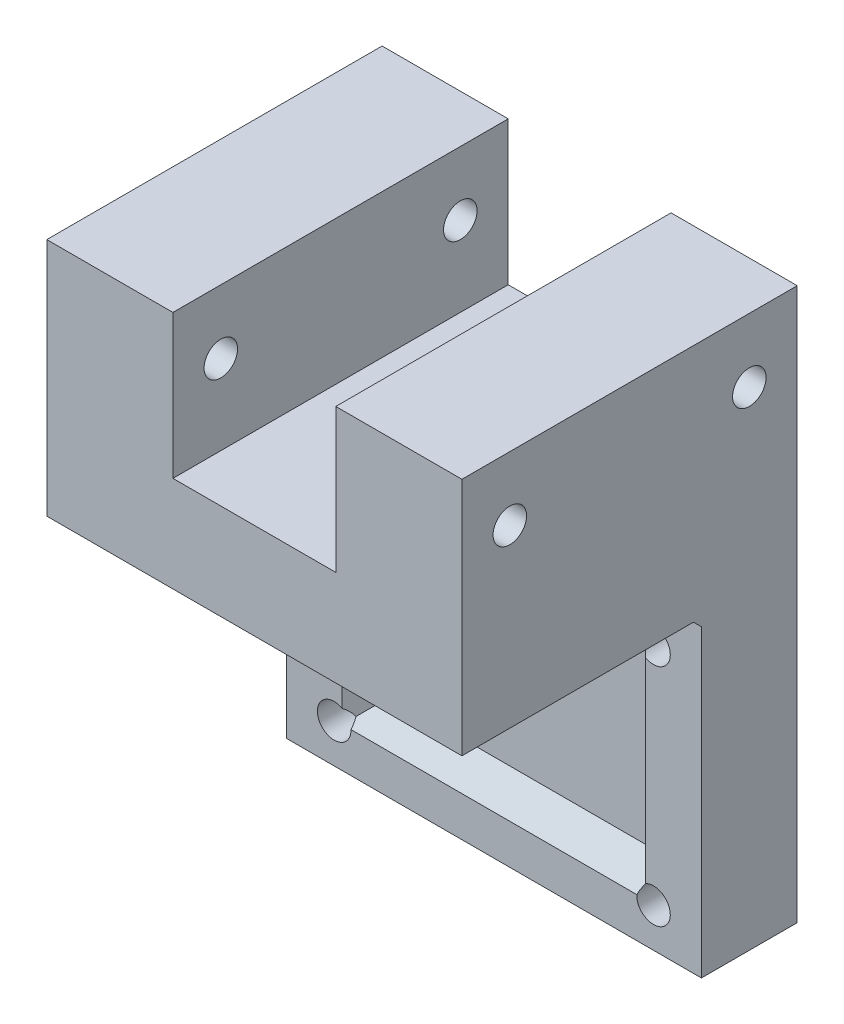
SolidWorks part; units mm, degrees
material "ABS"
ref_plane "Płaszczyzna przednia" through (0, 0, 0) normal (0, 0, 1) x (1, 0, 0)
ref_plane "Płaszczyzna górna" through (0, 0, 0) normal (0, 1, 0) x (1, 0, 0)
ref_plane "Płaszczyzna prawa" through (0, 0, 0) normal (1, 0, 0) x (0, 0, -1)
sketch "Szkic1" plane through (0, 0, 0) normal (0, 0, 1) x (1, 0, 0)
  line L0 (0, 25.3942) -> (0, -31.8647) construction
  line L1 (-26, -19) -> (26, -19)
  line L2 (-26, -19) -> (-26, 19)
  line L3 (-26, 19) -> (26, 19)
  line L4 (26, -19) -> (26, 19)
  line L5 (-26, -19) -> (26, 19) construction
  line L6 (-26, 19) -> (26, -19) construction
  line L7 (-29.318, 0) -> (39.6971, 0) construction
  circle A0 centre (20, 14.1) radius 2.1
  circle A1 centre (20, -14.1) radius 2.1
  circle A2 centre (-20, -14.1) radius 2.1
  circle A3 centre (-20, 14.1) radius 2.1
  point P0 (0, 0)
  dimension "D3" = 4.2
  dimension "D5" = 20
  dimension "D1" = 52
  dimension "D2" = 38
  dimension "D4" = 14.1
extrude "Dodanie-wyciągnięcie1" add sketch "Szkic1" along normal blind 12
sketch "Szkic2" plane through (0, 0, 12) normal (0, 0, 1) x (1, 0, 0)
  line L1 (16, -11) -> (-16, -11)
  line L2 (16, -11) -> (16, 11)
  line L3 (16, 11) -> (-16, 11)
  line L4 (-16, -11) -> (-16, 11)
  line L5 (16, -11) -> (-16, 11) construction
  line L6 (16, 11) -> (-16, -11) construction
  point P0 (0, 0)
  dimension "D1" = 32
  dimension "D2" = 22
extrude "Wytnij-wyciągnięcie1" cut sketch "Szkic2" against normal blind 3
chamfer "Sfazowanie1" distance 3 angle 45 4 edges at (0, -11, 12) (16, 0, 12) (-16, 0, 12) (0, 11, 12)
sketch "Szkic3" plane through (0, 0, 12) normal (0, 0, 1) x (1, 0, 0)
  line L0 (-20, 14.1) -> (-20, 32.1) construction
  line L1 (-10.2, 32.1) -> (10.2, 32.1)
  line L2 (26, 19) -> (-26, 19) construction
  line L3 (-10.2, 32.1) -> (-10.2, 50.1)
  line L4 (-10.2, 50.1) -> (-26, 50.1)
  line L5 (-26, 50.1) -> (-26, 19)
  line L6 (10.2, 32.1) -> (10.2, 50.1)
  line L7 (10.2, 50.1) -> (26, 50.1)
  line L8 (26, 50.1) -> (26, 19)
  line L9 (26, 19) -> (-26, 19)
  point P7 (0, 19)
  dimension "D1" = 18
  dimension "D2" = 20.4
  dimension "D3" = 10.2
  dimension "D4" = 18
extrude "Dodanie-wyciągnięcie2" add sketch "Szkic3" against normal blind 12
sketch "Szkic4" plane through (0, 0, 12) normal (0, 0, 1) x (1, 0, 0)
  line L0 (10.2, 32.1) -> (-10.2, 32.1) construction
  line L5 (0, 42.1305) -> (0, -22.2223) construction
  line L6 (-26, 20.1) -> (26, 20.1)
  line L7 (26, -19) -> (26, 50.1) construction
  line L12 (-26, 50.1) -> (-26, 20.1)
  line L13 (-26, 50.1) -> (-26, -19) construction
  line L14 (26, 20.1) -> (26, 50.1)
  line L15 (26, 50.1) -> (10.2, 50.1) construction
  line L16 (10.2, 50.1) -> (10.2, 32.1) construction
  line L17 (-10.2, 32.1) -> (-10.2, 50.1) construction
  line L18 (-10.2, 50.1) -> (-26, 50.1) construction
  line L19 (26, 50.1) -> (10.2, 50.1)
  line L20 (10.2, 50.1) -> (10.2, 32.1)
  line L21 (10.2, 32.1) -> (-10.2, 32.1)
  line L22 (-10.2, 32.1) -> (-10.2, 50.1)
  line L23 (-10.2, 50.1) -> (-26, 50.1)
  dimension "D1" = 12
extrude "Dodanie-wyciągnięcie3" add sketch "Szkic4" along normal blind 30
chamfer "Sfazowanie2" distance 1 angle 45 1 edges at (0, 20.1, 12)
sketch "Szkic6" plane through (26, 0, 0) normal (1, 0, 0) x (0, 0, -1)
  line L0 (0, 32.1) -> (-42, 32.1) construction
  line L1 (0, 32.1) -> (-42, 32.1) construction
  line L2 (-42, 20.1) -> (-42, 50.1) construction
  line L3 (-21, 32.1) -> (-21, 53.9853) construction
  circle A0 centre (-36, 42.1) radius 2.1
  circle A1 centre (-6, 42.1) radius 2.1
  dimension "D1" = 4.2
  dimension "D2" = 6
  dimension "D3" = 10
extrude "Wytnij-wyciągnięcie2" cut sketch "Szkic6" against normal through all
